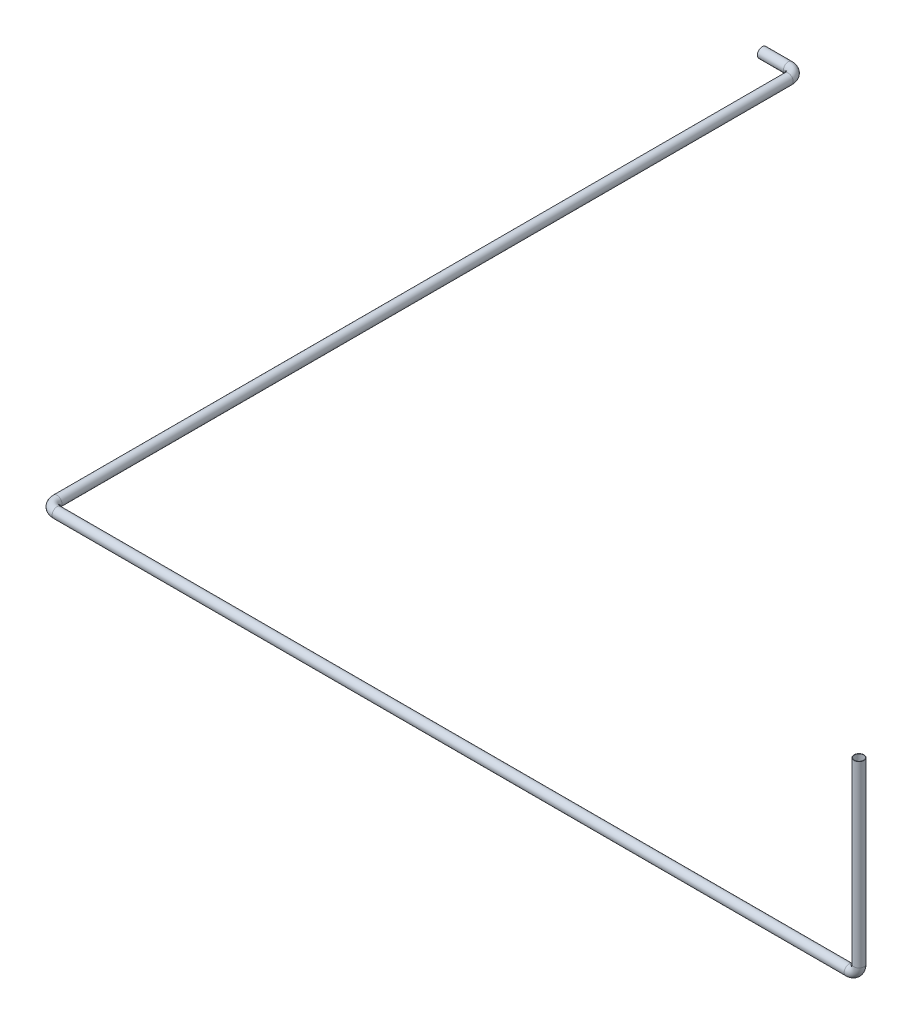
SolidWorks part; units mm, degrees
ref_plane "Plano frontal" through (0, 0, 0) normal (0, 0, 1) x (1, 0, 0)
ref_plane "Plano superior" through (0, 0, 0) normal (0, 1, 0) x (1, 0, 0)
ref_plane "Plano direito" through (0, 0, 0) normal (1, 0, 0) x (0, 0, -1)
sketch3d "3DSketch1"
  line L0 (-31937.4493, -16257.8595, 41333.8243) -> (-31937.4493, -16801.0208, 41333.8243)
  line L1 (-31937.4493, -16257.8595, 41163.2907) -> (-31937.4493, -16257.8595, 41543.1604) construction
  line L2 (-31967.4493, -16831.0208, 41333.8243) -> (-34374.4733, -16831.0208, 41333.8243)
  line L3 (-34404.4733, -16831.0208, 41303.8243) -> (-34404.4733, -16831.0208, 39081.7002)
  line L4 (-34434.4733, -16831.0208, 39051.7002) -> (-34513.5187, -16831.0208, 39051.7002)
  line L5 (-35073.5187, -16831.0208, 39051.7002) -> (-34513.5187, -16831.0208, 39051.7002) construction
  line L6 (-37122.8458, -16831.0208, 39051.7002) -> (-35073.5187, -16831.0208, 39051.7002) construction
  arc A0 (-31937.4493, -16801.0208, 41333.8243) -> (-31967.4493, -16831.0208, 41333.8243) centre (-31967.4493, -16801.0208, 41333.8243) ccw
  arc A1 (-34404.4733, -16831.0208, 39081.7002) -> (-34434.4733, -16831.0208, 39051.7002) centre (-34434.4733, -16831.0208, 39081.7002) ccw
  arc A2 (-34374.4733, -16831.0208, 41333.8243) -> (-34404.4733, -16831.0208, 41303.8243) centre (-34374.4733, -16831.0208, 41303.8243) ccw
  point P7 (0, 0, 0)
  point P10 (-34603.0622, -16831.0208, 39051.7002)
  point P11 (0, 0, 0)
  point P14 (0, 0, 0)
  point P16 (-31937.4493, -16831.0208, 41333.8243)
  point P17 (-31967.4493, -16801.0208, 41303.8243)
  point P20 (-34404.4733, -16831.0208, 39051.7002)
  point P21 (-34434.4733, -16801.0208, 39081.7002)
  point P24 (-34404.4733, -16831.0208, 41333.8243)
  point P25 (-34374.4733, -16861.0208, 41303.8243)
  dimension "D1" = 30
sweep "Sweep-Thin1" add path "3DSketch1" circular profile diameter 30 parameters "D1"=1, "D3"=30
